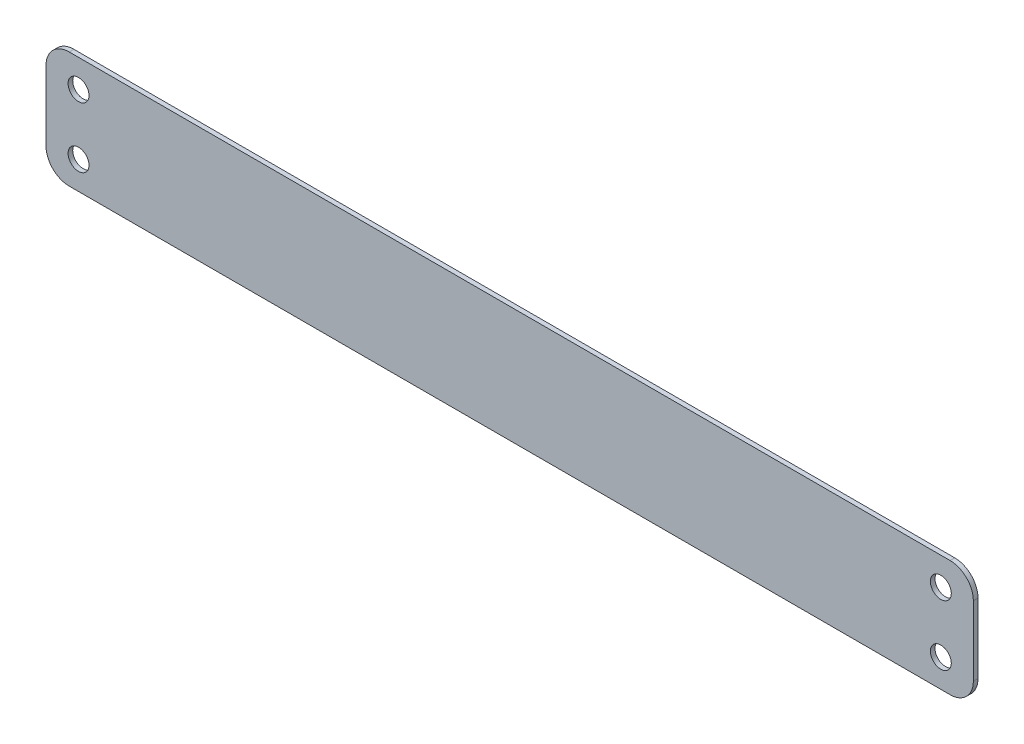
SolidWorks part; units mm, degrees
note: The reader was unsure of these and kept them because the rebuilt part matched: thickness of "Base-Flange1", "Sheet-Metal1", "Sheet-Metal2", "Sheet-Metal3".
material "AISI 304"
ref_plane "Front Plane" through (0, 0, 0) normal (0, 0, 1) x (1, 0, 0)
ref_plane "Top Plane" through (0, 0, 0) normal (0, 1, 0) x (1, 0, 0)
ref_plane "Right Plane" through (0, 0, 0) normal (1, 0, 0) x (0, 0, -1)
sketch "Sketch1" plane through (0, 0, 0) normal (0, 0, 1) x (1, 0, 0)
  line L1 (-199.5, -25) -> (199.5, -25)
  line L2 (-199.5, -25) -> (-199.5, 25)
  line L3 (-199.5, 25) -> (199.5, 25)
  line L4 (199.5, -25) -> (199.5, 25)
  line L5 (-199.5, -25) -> (199.5, 25) construction
  line L6 (-199.5, 25) -> (199.5, -25) construction
  point P0 (0, 0)
  dimension "D1" = 399
  dimension "D2" = 50
base flange "Base-Flange1" sketch "Sketch1" thickness 2 reverse thickness direction no parameters "D1"=4
fillet "Fillet1" radius 10 4 edges at (199.5, 25, -1) (-199.5, -25, -1) (199.5, -25, -1) (-199.5, 25, -1)
hole_wizard "M8 Clearance Hole1" positions "Sketch2" profile "Sketch3" hole size "M8" standard "ISO" end condition through all
sketch "Sketch2" plane through (0, 0, -2) normal (0, 0, -1) x (-1, 0, 0)
  line L0 (-185.5, 25) -> (-185.5, 13) construction
  line L1 (-189.5, 25) -> (189.5, 25) construction
  line L2 (-185.5, 13) -> (-185.5, -13) construction
  line L3 (-185.5, -13) -> (-185.5, -25) construction
  line L4 (189.5, -25) -> (-189.5, -25) construction
  line L6 (-199.5, -15) -> (-199.5, 15) construction
  point P0 (-185.5, 13)
  point P2 (-185.5, -13)
  dimension "D1" = 14
  dimension "D2" = 12
sketch "Sketch3" plane through (185.5, 13, -2) normal (1, 0, 0) x (0, 1, 0)
  line L0 (0, 0) -> (0, 2)
  line L1 (0, 2) -> (4.5, 2)
  line L2 (4.5, 2) -> (4.5, 0)
  line L5 (4.5, 0) -> (0, 0)
  line L11 (0, -6.35) -> (0, 107.95) construction
  dimension "Thru Hole Dia." = 9
  dimension "Thru Hole Depth" = 2
mirror "Mirror1" about plane through (0, 0, 0) normal (1, 0, 0) of "M8 Clearance Hole1"
sketch "Bend-Lines1" [suppressed] plane through (0, 0, 0) normal (0, 1, 0) x (1, 0, 0)
sketch "Bounding-Box1" [suppressed] plane through (0, 0, 0) normal (0, 1, 0) x (1, 0, 0)
sheet metal parameters "Sheet-Metal1" thickness 2 parameters "D1"=4, "D7"=3
flat pattern "Flat-Pattern1" [suppressed]
sketch "Bend-Lines2" plane through (0, 0, 0) normal (0, 1, 0) x (1, 0, 0)
sketch3d "Bounding-Box2" [suppressed]
  line L0 (-197, -15, 0) -> (197, -15, 0) construction
  line L1 (-197, 15, 0) -> (197, 15, 0) construction
  line L2 (-197, -15, 0) -> (-197, 15, 0) construction
  line L3 (197, -15, 0) -> (197, 15, 0) construction
sheet metal parameters "Sheet-Metal2" thickness 2 parameters "D1"=4, "D7"=3
flat pattern "Flat-Pattern1"
sketch "Bend-Lines2" plane through (0, 0, 0) normal (0, 1, 0) x (1, 0, 0)
sketch3d "Bounding-Box2" [suppressed]
  line L0 (-199.5, -25, 0) -> (199.5, -25, 0) construction
  line L1 (-199.5, 25, 0) -> (199.5, 25, 0) construction
  line L2 (-199.5, -25, 0) -> (-199.5, 25, 0) construction
  line L3 (199.5, -25, 0) -> (199.5, 25, 0) construction
sheet metal parameters "Sheet-Metal3" thickness 2 parameters "D1"=4, "D7"=3
flat pattern "Flat-Pattern1"
sketch "Bend-Lines2" plane through (0, 0, 0) normal (0, 1, 0) x (1, 0, 0)
sketch3d "Bounding-Box2" [suppressed]
  line L0 (-199.5, -25, 0) -> (199.5, -25, 0) construction
  line L1 (-199.5, 25, 0) -> (199.5, 25, 0) construction
  line L2 (-199.5, -25, 0) -> (-199.5, 25, 0) construction
  line L3 (199.5, -25, 0) -> (199.5, 25, 0) construction
